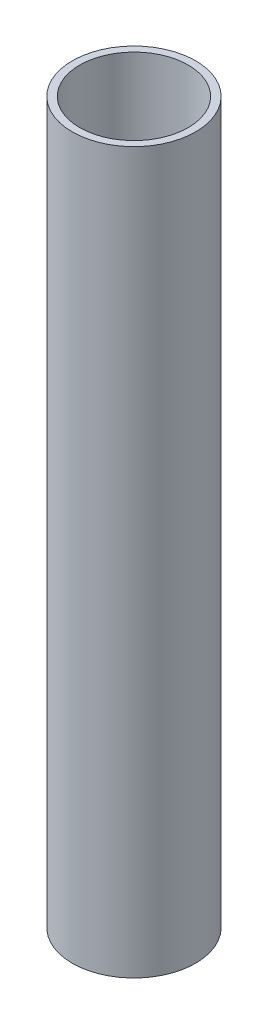
SolidWorks part; units mm, degrees
ref_plane "Front Plane" through (0, 0, 0) normal (0, 0, 1) x (1, 0, 0)
ref_plane "Top Plane" through (0, 0, 0) normal (0, 1, 0) x (1, 0, 0)
ref_plane "Right Plane" through (0, 0, 0) normal (1, 0, 0) x (0, 0, -1)
sketch "Sketch1" plane through (0, 0, 0) normal (0, 1, 0) x (1, 0, 0)
  circle A0 centre (0, 0) radius 1.25
  circle A1 centre (0, 0) radius 1.1
  dimension "D1" = 2.5
  dimension "D2" = 0.15
extrude "Boss-Extrude1" add sketch "Sketch1" along normal blind 14.6
